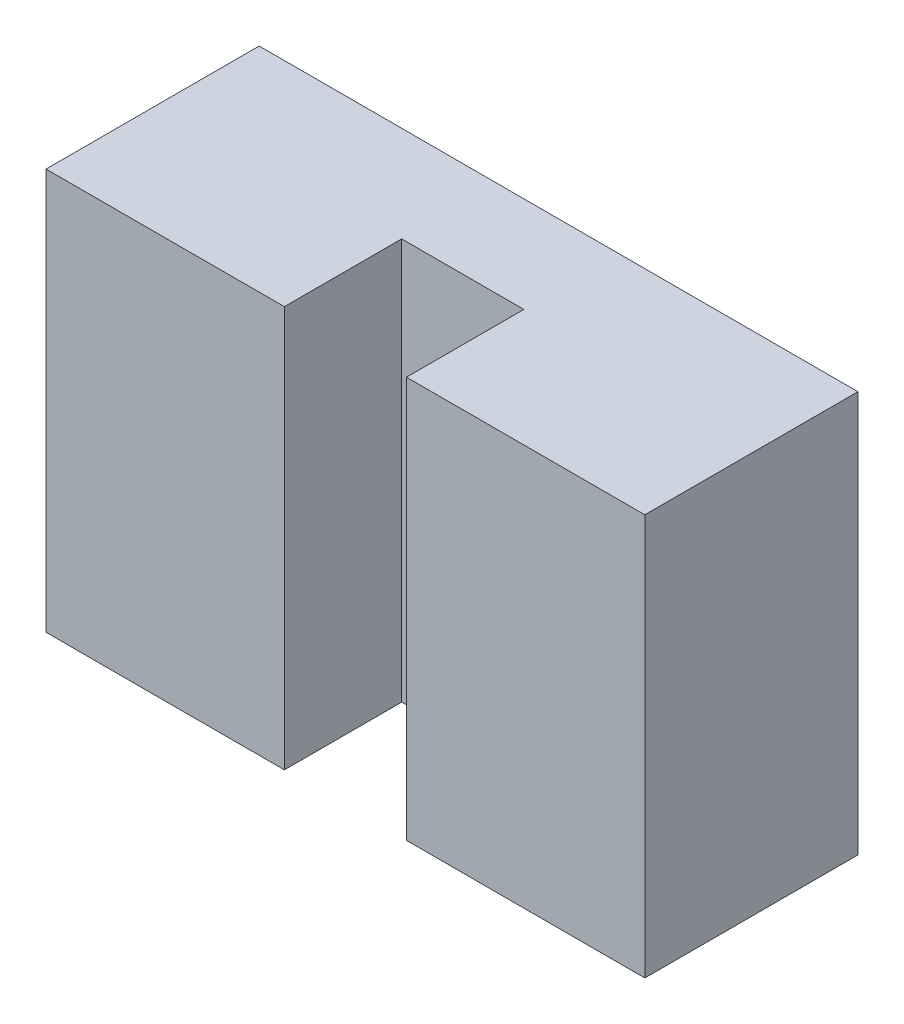
SolidWorks part; units mm, degrees
ref_plane "Спереди" through (0, 0, 0) normal (0, 0, 1) x (1, 0, 0)
ref_plane "Сверху" through (0, 0, 0) normal (0, 1, 0) x (1, 0, 0)
ref_plane "Справа" through (0, 0, 0) normal (1, 0, 0) x (0, 0, -1)
sketch "Sketch2" plane through (0, 0, 0) normal (0, 0, 1) x (1, 0, 0)
  line L0 (20, 0) -> (-20, 0) construction
  line L1 (25, -16.75) -> (-25, -16.75)
  line L2 (25, -16.75) -> (25, 16.75)
  line L3 (25, 16.75) -> (-25, 16.75)
  line L4 (-25, -16.75) -> (-25, 16.75)
  line L5 (25, -16.75) -> (-25, 16.75) construction
  line L6 (25, 16.75) -> (-25, -16.75) construction
  circle A0 centre (-20, 0) radius 1.75
  circle A1 centre (20, 0) radius 1.75
  point P0 (0, 0)
  point P9 (0, 0)
  dimension "D4" = 3.5
  dimension "D1" = 33.5
  dimension "D2" = 50
  dimension "D3" = 40
extrude "Boss-Extrude1" add sketch "Sketch2" along normal blind 8
sketch "Sketch5" plane through (0, -16.75, 0) normal (0, -1, 0) x (1, 0, 0)
  line L0 (-25, 8) -> (-25, 17.8)
  line L1 (-25, 8) -> (25, 8) construction
  line L2 (-25, 17.8) -> (-5.1, 17.8)
  line L3 (-5.1, 17.8) -> (-5.1, 8)
  line L4 (-5.1, 8) -> (5.1, 8)
  line L5 (5.1, 8) -> (5.1, 17.8)
  line L6 (5.1, 17.8) -> (25, 17.8)
  line L7 (25, 17.8) -> (25, 8)
  line L8 (25, 8) -> (-25, 8) construction
  line L9 (-25, 0) -> (25, 0) construction
  line L10 (0, 8) -> (0, 0) construction
  line L11 (-25, 8) -> (-25, 0) construction
  arc A0 (-25, 8) -> (25, 8) centre (0, 43.0625) ccw
  point P17 (0, 0)
  dimension "D1" = 10.2
  dimension "D3" = 9.8
extrude "Boss-Extrude2" add sketch "Sketch5" against normal up to surface (33.5 mm away) up to face at (0, 16.75, 4)
